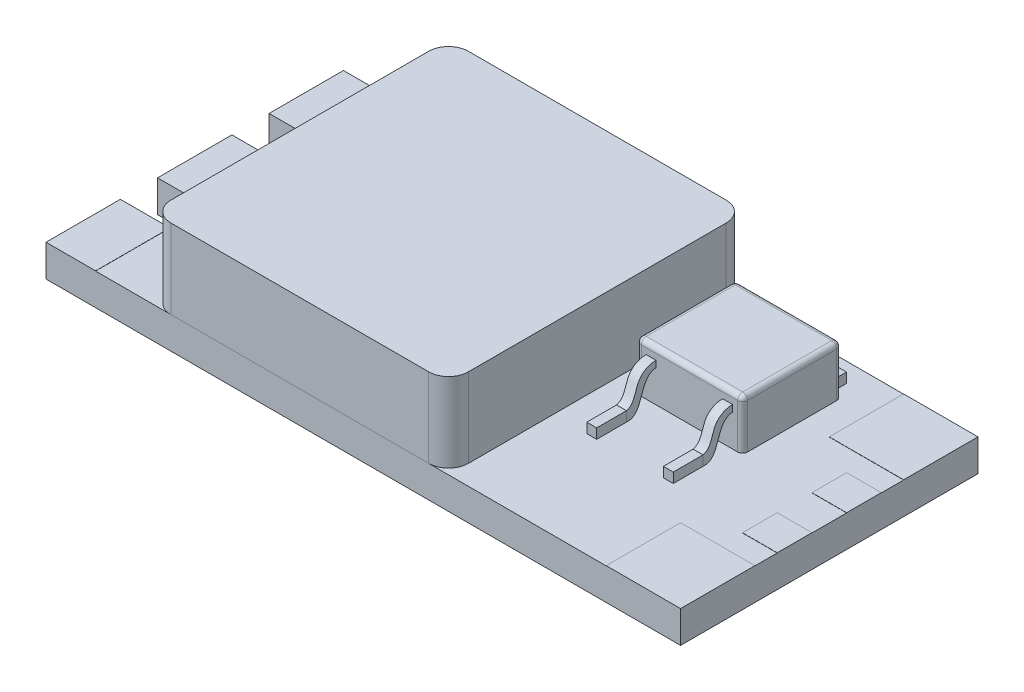
SolidWorks part; units mm, degrees
ref_plane "Front Plane" through (0, 0, 0) normal (0, 0, 1) x (1, 0, 0)
ref_plane "Top Plane" through (0, 0, 0) normal (0, 1, 0) x (1, 0, 0)
ref_plane "Right Plane" through (0, 0, 0) normal (1, 0, 0) x (0, 0, -1)
sketch "Sketch1" plane through (0, 0, 0) normal (0, 1, 0) x (1, 0, 0)
  line L0 (0, 3.75) -> (2.5, 3.75)
  line L1 (0, 0) -> (32, 0)
  line L2 (0, 0) -> (0, 3.75)
  line L3 (0, 15) -> (32, 15)
  line L4 (32, 0) -> (32, 15)
  line L5 (0, 0) -> (2.5, 0)
  line L6 (0, 0) -> (0, 3.75)
  line L7 (0, 15) -> (2.5, 15)
  line L8 (2.5, 3.75) -> (2.5, 5.625)
  line L9 (0, 11.25) -> (2.5, 11.25)
  line L10 (0, 11.25) -> (0, 15)
  line L11 (0, 9.375) -> (2.5, 9.375)
  line L12 (0, 9.375) -> (0, 5.625)
  line L13 (0, 5.625) -> (2.5, 5.625)
  line L15 (0, 11.25) -> (0, 15)
  line L16 (0, 5.625) -> (0, 9.375)
  line L17 (0, 5.625) -> (0, 9.375)
  line L18 (2.5, 9.375) -> (2.5, 11.25)
  dimension "D1" = 15
  dimension "D2" = 32
  dimension "D3" = 2.5
  dimension "D4" = 3.75
  dimension "D5" = 3.75
  dimension "D6" = 3.75
  dimension "D7" = 1.875
extrude "Boss-Extrude1" add sketch "Sketch1" along normal blind 1.6 contours L18 L11 L12 L13 L8 L0 L2 L1 L4 L3 L10 L9 region at (16.2938, 0, -7.5)
sketch "Sketch2" plane through (0, 1.6, 0) normal (0, 1, 0) x (1, 0, 0)
  line L0 (0, 0) -> (32, 0) construction
  line L1 (5.3, 0) -> (20.3, 0)
  line L2 (5.3, 0) -> (5.3, 15)
  line L3 (5.3, 15) -> (20.3, 15)
  line L4 (20.3, 0) -> (20.3, 15)
  line L5 (0, 15) -> (32, 15) construction
  line L6 (0, 9.375) -> (0, 5.625) construction
  dimension "D1" = 5.3
  dimension "D2" = 15
extrude "Boss-Extrude2" add sketch "Sketch2" along normal blind 4 separate body
fillet "Fillet1" radius 1 4 edges at (20.3, 3.6, 0) (20.3, 3.6, -15) (5.3, 3.6, -15) (5.3, 3.6, 0)
sketch "Sketch3" plane through (0, 1.6, 0) normal (0, 1, 0) x (1, 0, 0)
  line L0 (32, 7.5) -> (33.6122, 7.5)
  line L1 (0, 15) -> (2.5, 15)
  line L2 (0, 15) -> (0, 3.75)
  line L3 (0, 3.75) -> (2.5, 3.75)
  line L4 (2.5, 15) -> (2.5, 3.75)
  line L5 (0, 0) -> (2.5, 0)
  line L6 (0, 0) -> (0, 3.75)
  line L7 (0, 3.75) -> (2.5, 3.75)
  line L8 (2.5, 0) -> (2.5, 3.75)
  line L9 (32, 0) -> (28.25, 0)
  line L10 (32, 0) -> (32, 3.75)
  line L11 (32, 3.75) -> (28.25, 3.75)
  line L12 (2.5, 11.25) -> (2.5, 9.375)
  line L13 (2.5, 9.375) -> (0, 9.375)
  line L14 (0, 9.375) -> (0, 5.625)
  line L15 (0, 5.625) -> (2.5, 5.625)
  line L16 (2.5, 5.625) -> (2.5, 3.75)
  line L17 (2.5, 3.75) -> (0, 3.75)
  line L18 (0, 3.75) -> (0, 0)
  line L19 (0, 0) -> (32, 0)
  line L20 (32, 0) -> (32, 15)
  line L21 (32, 15) -> (0, 15)
  line L22 (0, 15) -> (0, 11.25)
  line L23 (0, 11.25) -> (2.5, 11.25)
  line L24 (2.5, 11.25) -> (2.5, 9.375)
  line L25 (2.5, 9.375) -> (0, 9.375)
  line L26 (0, 9.375) -> (0, 5.625)
  line L27 (0, 5.625) -> (2.5, 5.625)
  line L28 (2.5, 5.625) -> (2.5, 3.75)
  line L29 (2.5, 3.75) -> (0, 3.75)
  line L30 (0, 3.75) -> (0, 0)
  line L31 (0, 0) -> (32, 0)
  line L32 (32, 0) -> (32, 15)
  line L33 (32, 15) -> (0, 15)
  line L34 (0, 15) -> (0, 11.25)
  line L35 (0, 11.25) -> (2.5, 11.25)
  line L36 (28.25, 0) -> (28.25, 3.75)
  line L37 (32, 6.625) -> (30.25, 6.625)
  line L38 (32, 6.625) -> (32, 4.875)
  line L39 (32, 4.875) -> (30.25, 4.875)
  line L40 (30.25, 6.625) -> (30.25, 4.875)
  line L41 (30.25, 8.375) -> (30.25, 10.125)
  line L42 (32, 10.125) -> (30.25, 10.125)
  line L43 (32, 8.375) -> (32, 10.125)
  line L44 (32, 8.375) -> (30.25, 8.375)
  line L45 (28.25, 15) -> (28.25, 11.25)
  line L46 (32, 11.25) -> (28.25, 11.25)
  line L47 (32, 15) -> (32, 11.25)
  line L48 (32, 15) -> (28.25, 15)
  line M27 (2.5, 9.375) -> (0, 9.375)
  line M28 (0, 9.375) -> (0, 5.625)
  line M29 (0, 5.625) -> (2.5, 5.625)
  line M31 (2.5, 3.75) -> (0, 3.75)
  line M32 (0, 3.75) -> (0, 0)
  line M33 (0, 0) -> (32, 0)
  line M34 (32, 0) -> (32, 15)
  line M35 (32, 15) -> (0, 15)
  line M36 (0, 15) -> (0, 11.25)
  line M37 (0, 11.25) -> (2.5, 11.25)
  dimension "D2" = 3.75
  dimension "D3" = 3.75
  dimension "D4" = 1.75
  dimension "D5" = 1.75
  dimension "D6" = 0.875
  dimension "D1" = 0
extrude "Boss-Extrude3" add sketch "Sketch3" along normal blind 0.01 contours L46 L45 M34 M35 | L44 L32 L42 L41 | L37 L40 L39 L32 | L36 L11 M33 M34 | L4 M35 M36 M37 | L4 M27 M28 M29 | L8 M33 M31 M32 region at (1.25, 1.6, -13.125) region at (30.125, 1.6, -13.125) region at (1.25, 1.6, -7.5) region at (1.25, 1.6, -1.875) region at (31.125, 1.6, -9.25) region at (30.125, 1.6, -1.875) region at (31.125, 1.6, -5.75)
sketch "Sketch4" plane through (0, 1.6, 0) normal (0, 1, 0) x (1, 0, 0)
  line L1 (21.4824, 13.2754) -> (26.844, 13.2754)
  line L2 (21.4824, 13.2754) -> (21.4824, 8.2878)
  line L3 (21.4824, 8.2878) -> (26.844, 8.2878)
  line L4 (26.844, 13.2754) -> (26.844, 8.2878)
extrude "Boss-Extrude4" add sketch "Sketch4" along normal blind 2.5 contours L2 L1 L4 L3
sketch "Sketch6" plane through (0, 1.6, 0) normal (0, 1, 0) x (1, 0, 0)
  line L1 (21.9824, 13.2754) -> (26.344, 13.2754)
  line L2 (21.9824, 13.2754) -> (21.9824, 14.0254)
  line L3 (21.9824, 14.0254) -> (26.344, 14.0254)
  line L4 (21.4824, 8.2878) -> (26.844, 8.2878)
  line L5 (26.844, 8.2878) -> (26.844, 13.2754)
  line L6 (26.844, 13.2754) -> (21.4824, 13.2754)
  line L7 (21.4824, 13.2754) -> (21.4824, 8.2878)
  line L8 (21.4824, 8.2878) -> (26.844, 8.2878)
  line L9 (26.844, 8.2878) -> (26.844, 13.2754)
  line L10 (26.844, 13.2754) -> (21.4824, 13.2754)
  line L11 (21.4824, 13.2754) -> (21.4824, 8.2878)
  line L12 (26.344, 13.2754) -> (26.344, 14.0254)
  line L14 (21.9824, 8.2878) -> (22.4824, 8.2878)
  line L15 (21.9824, 8.2878) -> (21.9824, 5.2878)
  line L16 (21.9824, 5.2878) -> (22.4824, 5.2878)
  line L17 (22.4824, 8.2878) -> (22.4824, 5.2878)
  line L18 (26.344, 8.2878) -> (25.844, 8.2878)
  line L19 (26.344, 8.2878) -> (26.344, 5.2878)
  line L20 (26.344, 5.2878) -> (25.844, 5.2878)
  line L21 (25.844, 8.2878) -> (25.844, 5.2878)
  line L22 (25.844, 5.2878) -> (26.344, 5.2878)
  line L23 (25.844, 5.2878) -> (25.844, 6.6282)
  line L25 (26.344, 5.2878) -> (26.344, 6.6282)
  line L26 (21.9824, 5.2878) -> (22.4824, 5.2878)
  line L27 (21.9824, 5.2878) -> (21.9824, 6.7878)
  line L28 (21.9824, 6.7878) -> (22.4824, 6.7878)
  line L29 (22.4824, 5.2878) -> (22.4824, 6.7878)
  line L30 (25.844, 5.2878) -> (26.344, 5.2878)
  line L31 (25.844, 5.2878) -> (25.844, 6.7878)
  line L32 (25.844, 6.7878) -> (26.344, 6.7878)
  line L33 (26.344, 5.2878) -> (26.344, 6.7878)
  line M38 (21.4824, 13.2754) -> (26.844, 13.2754)
  dimension "D2" = 0.75
  dimension "D3" = 0.5
  dimension "D4" = 0.5
  dimension "D5" = 0.5
  dimension "D6" = 0.5
  dimension "D7" = 0.5
  dimension "D8" = 0.5
  dimension "D9" = 3
  dimension "D10" = 3
  dimension "D1" = 0
extrude "Boss-Extrude5" add sketch "Sketch6" along normal blind 0.5 separate body contours L32 L21 L20 L19 | L28 L15 L16 L17 | L12 L3 L2 M38 region at (24.1632, 1.6, -13.6504) region at (22.2324, 1.6, -6.0378) region at (26.094, 1.6, -6.0378)
sketch "Sketch7" plane through (26.344, 0, 0) normal (1, 0, 0) x (0, 0, -1)
  line L0 (8.2878, 4.1) -> (8.2878, 1.6) construction
  line L1 (8.2878, 3.2266) -> (8.2878, 3.5498)
  line L5 (5.2878, 1.6) -> (6.7878, 1.6)
  line L6 (6.7878, 1.6) -> (6.7878, 2.1)
  line L7 (6.7878, 2.1) -> (5.2878, 2.1)
  line L8 (5.2878, 2.1) -> (5.2878, 1.6)
  line L9 (5.2878, 1.6) -> (6.7878, 1.6)
  line L10 (6.7878, 1.6) -> (6.7878, 2.1)
  line L11 (6.7878, 2.1) -> (5.2878, 2.1)
  line L12 (5.2878, 2.1) -> (5.2878, 1.6)
  spline S0 degree 3 poles (6.7878, 1.6) (7.7188, 1.5101) (7.3747, 3.1846) (8.2878, 3.2266) knots 0 0 0 0 1 1 1 1
  spline S1 degree 3 poles (6.7878, 2.1) (7.2302, 2.2154) (7.1923, 3.1943) (7.9475, 3.5661) (8.2878, 3.5498) knots 0 0 0 0 0.555689 1 1 1 1
  line M6 (6.7878, 1.6) -> (6.7878, 2.1)
  dimension "D1" = 0
extrude "Boss-Extrude6" add sketch "Sketch7" against normal blind 0.5 separate body contours S1 S0 L1 M6 region at (26.344, 2.5958, -7.4565)
sketch "Sketch8" plane through (22.4824, 0, 0) normal (1, 0, 0) x (0, 0, -1)
  line L2 (6.7878, 2.1) -> (6.7878, 1.6)
  line L3 (8.2878, 3.2266) -> (8.2878, 3.5498)
  line L4 (6.7878, 2.1) -> (6.7878, 1.6)
  line L5 (8.2878, 3.2266) -> (8.2878, 3.5498)
  spline S2 degree 3 poles (-3511.9072, -1889.7291) (155.4518, -85.1759) (-86.9811, 79.1505) (67.1071, -60.0327) (-3013.5054, 2624.1531) knots -12.718445 -12.718445 -12.718445 -12.718445 0.444311 9.641193 9.641193 9.641193 9.641193 only from (8.2878, 3.5498) to (6.7878, 2.1)
  spline S3 degree 3 poles (-2392.4799, 3201.947) (2401.1783, -3225.8398) (-2391.0138, 3226.8555) (2422.4372, -3185.8128) knots -9.307914 -9.307914 -9.307914 -9.307914 10.335231 10.335231 10.335231 10.335231 only from (6.7878, 1.6) to (8.2878, 3.2266)
  spline S4 degree 3 poles (8.2878, 3.5498) (7.9475, 3.5661) (7.1923, 3.1943) (7.2302, 2.2154) (6.7878, 2.1) knots 0 0 0 0 0.444311 1 1 1 1
  spline S5 degree 3 poles (6.7878, 1.6) (7.7188, 1.5101) (7.3747, 3.1846) (8.2878, 3.2266) knots 0 0 0 0 1 1 1 1
  dimension "D1" = 0
extrude "Boss-Extrude7" add sketch "Sketch8" against normal blind 0.5 separate body
fillet "Fillet2" radius 0.25 4 edges at (21.4824, 2.85, -13.2754) (21.4824, 2.85, -8.2878) (26.844, 2.85, -8.2878) (26.844, 2.85, -13.2754)
fillet "Fillet3" radius 0.25 8 edges at (26.7708, 4.1, -13.2021) (26.844, 4.1, -10.7816) (26.7708, 4.1, -8.361) (24.1632, 4.1, -8.2878) (21.5557, 4.1, -8.361) (21.4824, 4.1, -10.7816) (21.5557, 4.1, -13.2021) (24.1632, 4.1, -13.2754)
